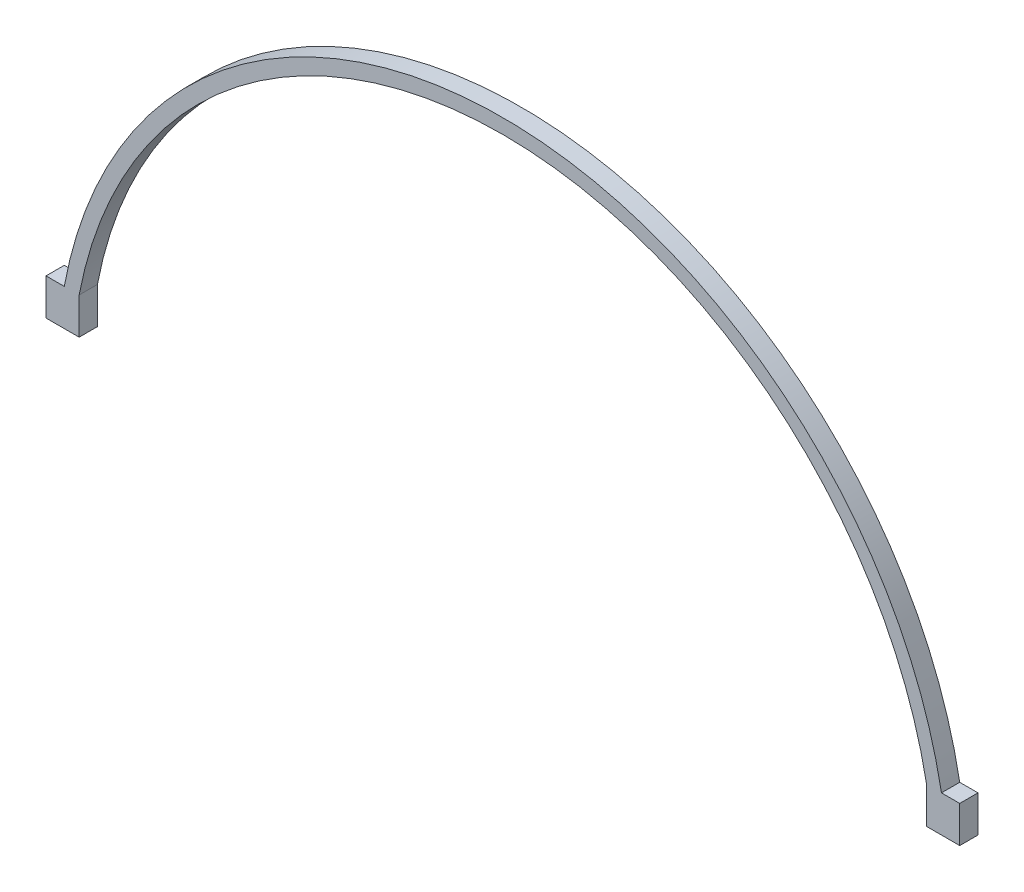
SolidWorks part; units mm, degrees
ref_plane "Front" through (0, 0, 0) normal (0, 0, 1) x (1, 0, 0)
ref_plane "Top" through (0, 0, 0) normal (0, 1, 0) x (1, 0, 0)
ref_plane "Right" through (0, 0, 0) normal (1, 0, 0) x (0, 0, -1)
sketch "Sketch1" plane through (0, 0, 0) normal (0, 0, 1) x (1, 0, 0)
  line L0 (-76.2, 0) -> (76.2, 0) construction
  line L1 (0, 0) -> (0, 63.5) construction
  line L2 (-76.2, 0) -> (-73.6162, 0)
  line L3 (76.2, 0) -> (73.6162, 0)
  arc A0 (-76.2, 0) -> (76.2, 0) centre (0, -13.97) cw
  arc A1 (-73.6162, 0) -> (73.6162, 0) centre (0, -13.97) cw
  arc A2 (-73.7016, -0.458) -> (73.7016, -0.458) centre (0, -13.97) cw construction
  point P4 (0, 0)
  dimension "D1" = 152.4
  dimension "D2" = 63.5
  dimension "D3" = 2.54
extrude "Boss-Extrude1" add sketch "Sketch1" along normal blind 3.175 contours A1 L3 A0 L2
sketch "Sketch2" plane through (0, 0, 0) normal (0, -1, 0) x (1, 0, 0)
  line L0 (76.2, 3.175) -> (76.2, 0) construction
  line L1 (73.6162, 0) -> (79.375, 0)
  line L2 (73.6162, 0) -> (73.6162, 3.175)
  line L3 (73.6162, 3.175) -> (79.375, 3.175)
  line L4 (79.375, 0) -> (79.375, 3.175)
  line L5 (76.2, 3.175) -> (73.6162, 3.175) construction
  line L6 (0, 0) -> (0, 87.8542) construction
  line L7 (-73.6162, 0) -> (73.6162, 0) construction
  line L8 (-73.6162, 3.175) -> (-79.375, 3.175)
  line L9 (-79.375, 0) -> (-79.375, 3.175)
  line L10 (-73.6162, 0) -> (-79.375, 0)
  line L11 (-73.6162, 0) -> (-73.6162, 3.175)
  dimension "D1" = 3.175
extrude "Boss-Extrude2" add sketch "Sketch2" along normal blind 6.35
